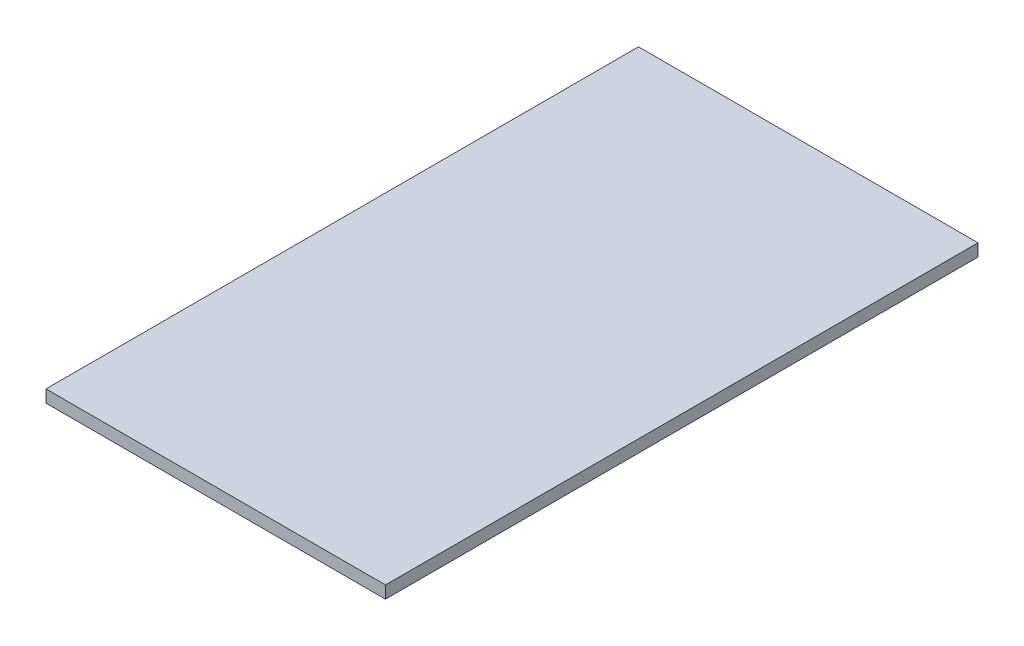
SolidWorks part; units mm, degrees
material "PCB (FR-4) (Recolor)"
ref_plane "Front Plane" through (0, 0, 0) normal (0, 0, 1) x (1, 0, 0)
ref_plane "Top Plane" through (0, 0, 0) normal (0, 1, 0) x (1, 0, 0)
ref_plane "Right Plane" through (0, 0, 0) normal (1, 0, 0) x (0, 0, -1)
sketch "Sketch2" plane through (0, 0, 0) normal (0, 1, 0) x (1, 0, 0)
  line L1 (0, 0) -> (55, 0)
  line L2 (0, 0) -> (0, 96)
  line L3 (0, 96) -> (55, 96)
  line L4 (55, 0) -> (55, 96)
  dimension "D1" = 96
  dimension "D2" = 55
extrude "Boss-Extrude1" add sketch "Sketch2" along normal blind 2
sketch "Sketch3" [suppressed] plane through (0, 2, 0) normal (0, 1, 0) x (1, 0, 0)
  line L0 (2.5, 2.5) -> (52.5, 2.5) construction
  line L1 (52.5, 2.5) -> (52.5, 93.5) construction
  line L2 (0, 0) -> (55, 0) construction
  line L3 (55, 0) -> (55, 96) construction
  line L4 (0, 96) -> (0, 0) construction
  line L5 (55, 96) -> (0, 96) construction
  line L6 (2.5, 93.5) -> (52.5, 93.5) construction
  line L9 (2.5, 93.5) -> (2.5, 2.5) construction
  circle A0 centre (2.5, 2.5) radius 0.762
  circle A1 centre (52.5, 2.5) radius 0.762
  circle A2 centre (52.5, 93.5) radius 0.762
  circle A3 centre (2.5, 93.5) radius 0.762
  dimension "D1" = 1.524
  dimension "D2" = 2.5
  dimension "D3" = 2.5
  dimension "D4" = 2.5
  dimension "D5" = 2.5
extrude "Cut-Extrude1" [suppressed] cut sketch "Sketch3" against normal through all
